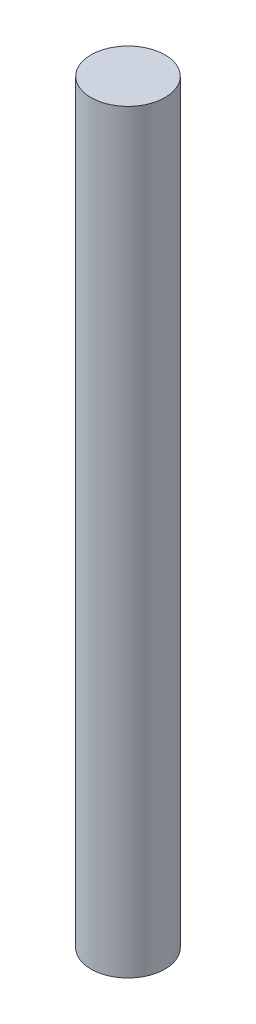
SolidWorks part; units mm, degrees
ref_plane "Front Plane" through (0, 0, 0) normal (0, 0, 1) x (1, 0, 0)
ref_plane "Top Plane" through (0, 0, 0) normal (0, 1, 0) x (1, 0, 0)
ref_plane "Right Plane" through (0, 0, 0) normal (1, 0, 0) x (0, 0, -1)
sketch "Sketch1" plane through (0, 0, 0) normal (0, 1, 0) x (1, 0, 0)
  circle A0 centre (0, 0) radius 12.446
  dimension "D1" = 24.892
extrude "Boss-Extrude1" add sketch "Sketch1" along normal blind 254
